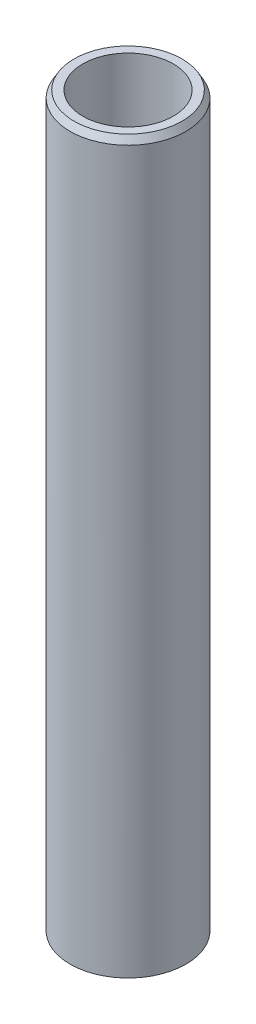
SolidWorks part; units mm, degrees
ref_plane "Front Plane" through (0, 0, 0) normal (0, 0, 1) x (1, 0, 0)
ref_plane "Top Plane" through (0, 0, 0) normal (0, 1, 0) x (1, 0, 0)
ref_plane "Right Plane" through (0, 0, 0) normal (1, 0, 0) x (0, 0, -1)
sketch "Sketch1" plane through (0, 0, 0) normal (0, 1, 0) x (1, 0, 0)
  circle A0 centre (0, 0) radius 47.5
  dimension "SHAFT_OD" = 95
extrude "Boss-Extrude1" add sketch "Sketch1" along normal blind 600
sketch "Sketch2" plane through (0, 0, 0) normal (0, 1, 0) x (1, 0, 0)
  circle A0 centre (0, 0) radius 37.1473
  dimension "BORE_D" = 74.2946
extrude "Cut-Extrude1" cut sketch "Sketch2" along normal through all
chamfer "Chamfer1" distance 5.626 angle 30 2 edges at (0, 600, 47.5) (0, 0, 47.5) first distance on face at (0, 600, 47.5) first distance on face at (0, 0, 37.1473)
